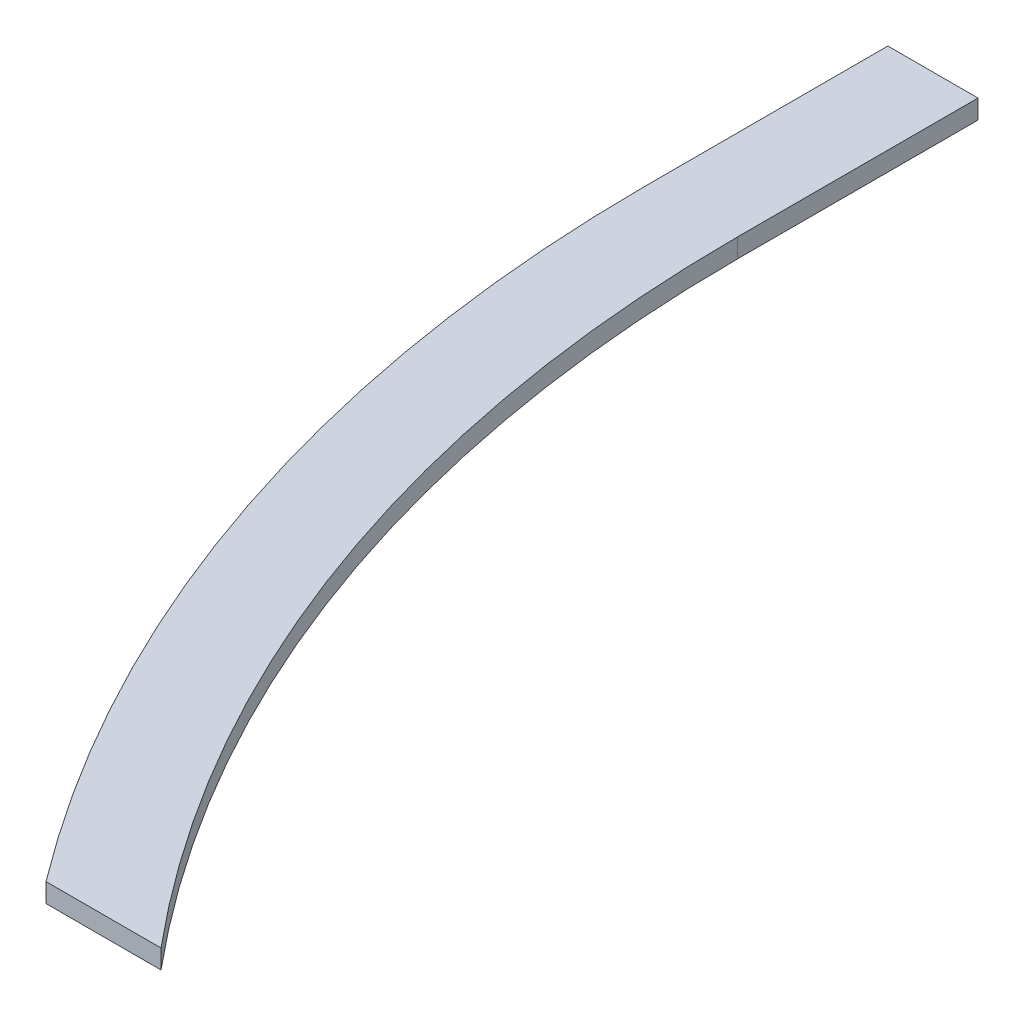
SolidWorks part; units mm, degrees
material "Pine"
ref_plane "Front Plane" through (0, 0, 0) normal (0, 0, 1) x (1, 0, 0)
ref_plane "Top Plane" through (0, 0, 0) normal (0, 1, 0) x (1, 0, 0)
ref_plane "Right Plane" through (0, 0, 0) normal (1, 0, 0) x (0, 0, -1)
sketch "Sketch2" plane through (0, 0, 0) normal (0, 1, 0) x (1, 0, 0)
  line L0 (0, 0) -> (-500, 0)
  line L1 (0, 0) -> (0, -500)
  circle A0 centre (0, 0) radius 500
  circle A1 centre (0, 0) radius 470
  dimension "D1" = 1000
  dimension "D2" = 30
extrude "Boss-Extrude1" add sketch "Sketch2" along normal blind 6.35 contours A1 L0 A0 L1 region at (-337.3402, 0, 337.3402)
sketch "Sketch3" plane through (0, 0, 0) normal (0, 0, -1) x (-1, 0, 0)
  line L8 (470, 0) -> (500, 0)
  line L9 (500, 0) -> (500, 6.35)
  line L10 (500, 6.35) -> (470, 6.35)
  line L11 (470, 6.35) -> (470, 0)
  line L12 (470, 0) -> (500, 0)
  line L13 (500, 0) -> (500, 6.35)
  line L14 (500, 6.35) -> (470, 6.35)
  line L15 (470, 6.35) -> (470, 0)
  dimension "D1" = 0
extrude "Boss-Extrude2" add sketch "Sketch3" along normal blind 80
sketch "Sketch4" plane through (0, 6.35, 0) normal (0, 1, 0) x (1, 0, 0)
  line L1 (-500, 80) -> (0, 80) construction
  line L2 (-500, 80) -> (-500, -500) construction
  line L3 (-500, -500) -> (0, -500) construction
  line L4 (0, 80) -> (0, -500) construction
  line L5 (-500, 80) -> (-195.2, 80) construction
  line L6 (-500, 80) -> (-500, -326.4) construction
  line L7 (-500, -326.4) -> (-195.2, -326.4) construction
  line L8 (-195.2, 80) -> (-195.2, -326.4) construction
  line L9 (0, -500) -> (-406.4, -500) construction
  line L10 (0, -500) -> (0, -195.2) construction
  line L11 (0, -195.2) -> (-406.4, -195.2) construction
  line L12 (-406.4, -500) -> (-406.4, -195.2) construction
  dimension "D1" = 304.8
  dimension "D2" = 406.4
  dimension "D3" = 304.8
  dimension "D4" = 406.4
ref_plane "Plane1" through (0, 0, 301) normal (0, 0, -1) x (-1, 0, 0)
split "Split1" trim tools "Plane1" bodies to split 102 resulting bodies 104
